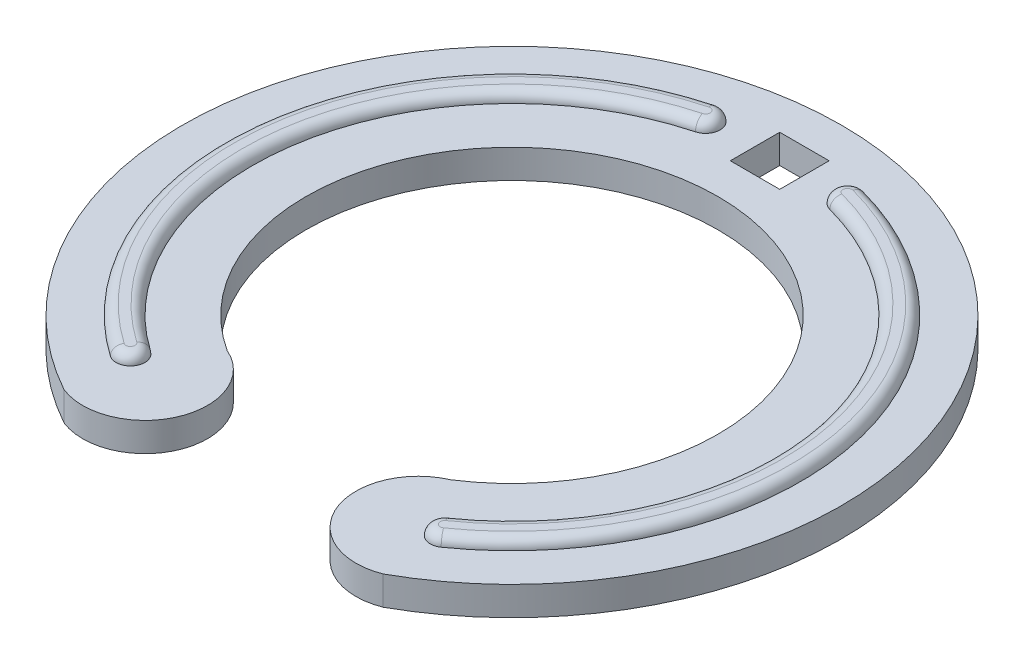
SolidWorks part; units mm, degrees
ref_plane "Plan de face" through (0, 0, 0) normal (0, 0, 1) x (1, 0, 0)
ref_plane "Plan de dessus" through (0, 0, 0) normal (0, 1, 0) x (1, 0, 0)
ref_plane "Plan de droite" through (0, 0, 0) normal (1, 0, 0) x (0, 0, -1)
sketch "Esquisse1" plane through (0, 0, 0) normal (0, 1, 0) x (1, 0, 0)
  line L2 (0, 40) -> (0, -61.5139) construction
  line L5 (-3, 35.5) -> (3, 35.5)
  line L6 (-3, 35.5) -> (-3, 29.5)
  line L7 (-3, 29.5) -> (3, 29.5)
  line L8 (3, 35.5) -> (3, 29.5)
  arc A0 (19.3649, -35) -> (-19.3649, -35) centre (0, 0) ccw
  arc A1 (13.5647, -21) -> (-13.5647, -21) centre (0, 0) ccw
  arc A2 (-19.3649, -35) -> (-13.5647, -21) centre (-16.5824, -27.9513) ccw
  arc A3 (19.3649, -35) -> (13.5647, -21) centre (16.5824, -27.9513) cw
  point P4 (0, 32.5)
  point P15 (-3, 32.5)
  dimension "D1" = 15
  dimension "D3" = 40
  dimension "D2" = 32.5
  dimension "D5" = 21
  dimension "D4" = 27.1293
  dimension "D6" = 32.5
  dimension "D7" = 7.5781
  dimension "D8" = 3
  dimension "D9" = 3
  dimension "D10" = 6
  dimension "D11" = 6
extrude "Boss.-Extru.2" add sketch "Esquisse1" along normal blind 3.5
sketch "Esquisse5" plane through (0, 3.5, 0) normal (0, 1, 0) x (1, 0, 0)
  line L0 (0, 0) -> (-10.9444, 40.845) construction
  line L1 (0, 0) -> (-25.3528, -36.2076) construction
  line L2 (0, 0) -> (0, 21.3933) construction
  arc A0 (-20.0752, -28.6703) -> (-9.0587, 33.8074) centre (0, 0) cw
  arc A1 (-18.0677, -25.8033) -> (-8.1528, 30.4267) centre (0, 0) cw
  arc A2 (-9.0587, 33.8074) -> (-8.1528, 30.4267) centre (-8.6057, 32.117) cw
  arc A3 (-18.0677, -25.8033) -> (-20.0752, -28.6703) centre (-19.0714, -27.2368) cw
  dimension "D3" = 35
  dimension "D4" = 3.5
  dimension "D1" = 15
  dimension "D2" = 35
extrude "Boss.-Extru.3" add sketch "Esquisse5" along normal blind 1.2
fillet "Congé2" radius 1.2 4 edges at (-34.4683, 4.7, -6.0777) (-6.9154, 4.7, -32.57) (-31.0214, 4.7, -5.4699) (-17.6379, 4.7, 28.2406)
mirror "Symétrie2" about plane through (0, 0, 0) normal (1, 0, 0) of "Congé2", "Boss.-Extru.3"
